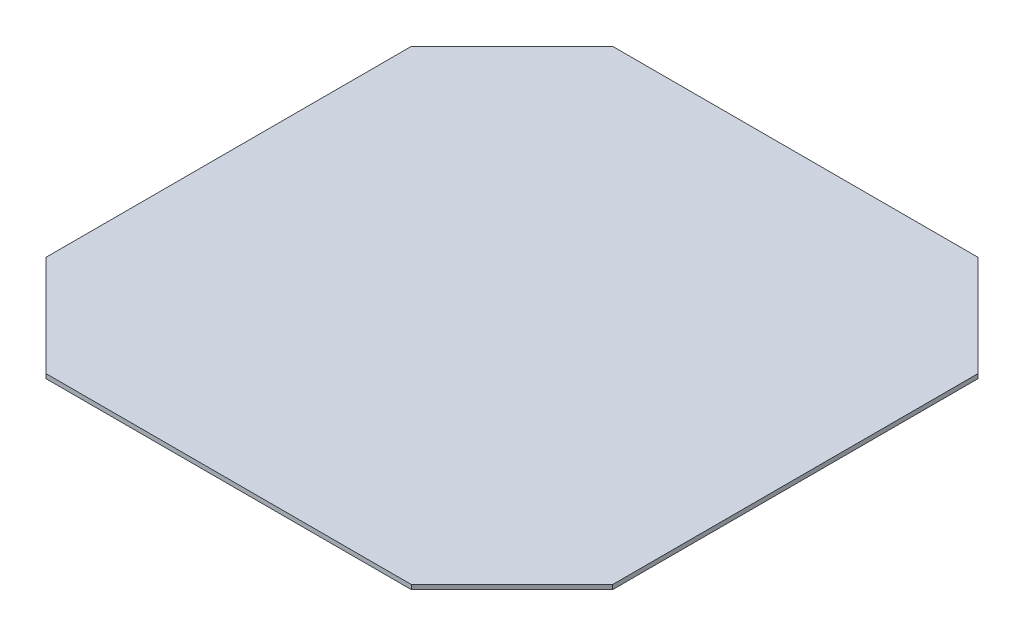
SolidWorks part; units mm, degrees
ref_plane "Front Plane" through (0, 0, 0) normal (0, 0, 1) x (1, 0, 0)
ref_plane "Top Plane" through (0, 0, 0) normal (0, 1, 0) x (1, 0, 0)
ref_plane "Right Plane" through (0, 0, 0) normal (1, 0, 0) x (0, 0, -1)
sketch "Sketch1" plane through (0, 0, 0) normal (0, 1, 0) x (1, 0, 0)
  line L0 (0, 606.425) -> (0, -606.425) construction
  line L1 (-606.425, 606.425) -> (606.425, 606.425)
  line L2 (-606.425, 606.425) -> (-606.425, -606.425)
  line L3 (-606.425, -606.425) -> (606.425, -606.425)
  line L4 (606.425, 606.425) -> (606.425, -606.425)
  dimension "D1" = 1212.85
  dimension "D2" = 1212.85
extrude "Boss-Extrude1" add sketch "Sketch1" along normal blind 9.525
sketch "Sketch2" plane through (0, 9.525, 0) normal (0, 1, 0) x (1, 0, 0)
  line L0 (0, -606.425) -> (0, 606.425) construction
  line L1 (-606.425, -606.425) -> (606.425, -606.425) construction
  line L2 (606.425, 606.425) -> (-606.425, 606.425) construction
  line L3 (-606.425, 0) -> (606.425, 0) construction
  line L4 (-606.425, 606.425) -> (-606.425, -606.425) construction
  line L5 (606.425, -606.425) -> (606.425, 606.425) construction
  circle A0 centre (-606.425, 606.425) radius 152.4
  circle A1 centre (-606.425, -606.425) radius 152.4
  circle A2 centre (606.425, -606.425) radius 152.4
  circle A3 centre (606.425, 606.425) radius 152.4
  point P20 (-606.425, 758.825)
  point P21 (-758.825, 606.425)
  dimension "D1" = 304.8
extrude "Cut-Extrude1" cut sketch "Sketch2" against normal up to next
sketch "Sketch3" plane through (0, 9.525, 0) normal (0, 1, 0) x (1, 0, 0)
  line L0 (390.8989, 606.425) -> (606.425, 390.8989)
  line L1 (454.025, 606.425) -> (-454.025, 606.425) construction
  line L2 (606.425, -454.025) -> (606.425, 454.025) construction
  line L3 (390.8989, 606.425) -> (606.425, 606.425) construction
  line L4 (606.425, 606.425) -> (606.425, 390.8989) construction
  circle A0 centre (606.425, 606.425) radius 152.4 construction
extrude "Cut-Extrude2" cut sketch "Sketch3" against normal through all and the other way through all
mirror "Mirror1" about plane through (0, 0, 0) normal (0, 0, 1) of "Cut-Extrude2"
mirror "Mirror2" about plane through (0, 0, 0) normal (1, 0, 0) of "Mirror1", "Cut-Extrude2"
